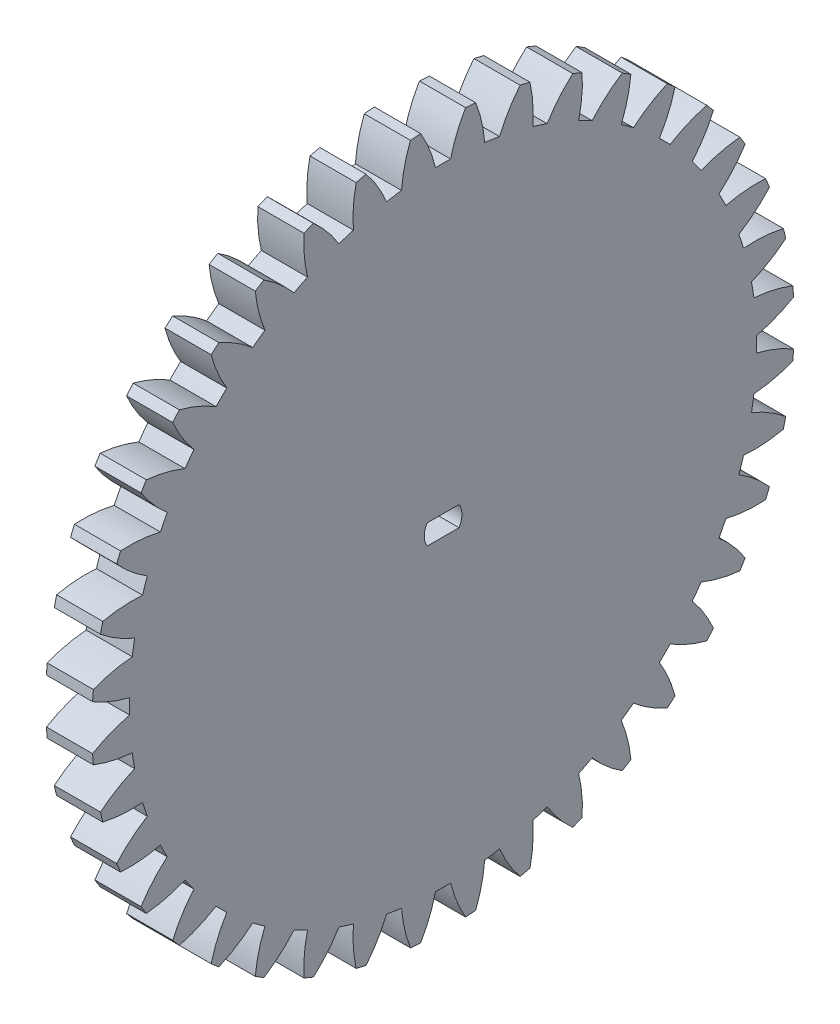
SolidWorks part; units mm, degrees
ref_plane "Plane1" through (0, 0, 0) normal (0, 0, 1) x (1, 0, 0)
ref_plane "Plane2" through (0, 0, 0) normal (0, 1, 0) x (1, 0, 0)
ref_plane "Plane3" through (0, 0, 0) normal (1, 0, 0) x (0, 0, -1)
sketch "HoldingSke" plane through (0, 0, 0) normal (0, 1, 0) x (1, 0, 0)
  line L0 (0, 0) -> (233.4903, -195.9217)
  line L1 (-15, 0) -> (100, 0) construction
  line L2 (0, 0) -> (-2.1039, 2.3779)
  line L3 (0, 0) -> (-11.863, 4.5341)
  line L4 (0, 0) -> (6.6156, 5.5511)
  line L5 (0, 0) -> (-47.5972, -17.7524)
  line L6 (0, 0) -> (-4.8428, -3.2675)
  line L7 (-2.1039, 2.3779) -> (8.8308, 51.9871)
  line L8 (-76.2, 54.61) -> (-71.1708, 54.61)
  line L9 (-71.009, 38.7566) -> (-53.1078, 45.2721)
  line L10 (-76.2, 71.12) -> (104.1128, 71.12)
  line L11 (0, 0) -> (-5.842, 0)
  line L12 (-76.2, 101.6) -> (-76.1147, 101.6)
  line L13 (24.9733, 27.94) -> (52.9518, 28.4284)
  line L14 (24.9733, 27.94) -> (24.9746, 27.94)
  line L15 (24.9733, 27.94) -> (100.4006, 29.5858)
  circle A0 centre (0, 0) radius 2.3813
  circle A1 centre (0, 0) radius 38.1
  circle A2 centre (0, 0) radius 38.1
  circle A3 centre (0, 0) radius 2.3813
  dimension "Num_teeth" = 40
  dimension "H" = 19.05
  dimension "Pitch_radius" = 180.3128
  dimension "Width" = 5.842
  dimension "Thickness" = 5.842
sketch "BasProSke" plane through (0, 0, 0) normal (0, 1, 0) x (1, 0, 0)
  line L0 (-10, 0) -> (60, 0) construction
  line L1 (0, 0) -> (0, 44.45)
  line L2 (0, 0) -> (5.842, 0)
  line L3 (5.842, 0) -> (5.842, 44.45)
  line L4 (5.842, 44.45) -> (0, 44.45)
  dimension "Thickness" = 5.842
  dimension "Diameter" = 88.9
revolve "Base-Revolve" add sketch "BasProSke" angle 360 about L0
sketch "TooCutSke" plane through (0, 0, 0) normal (1, 0, 0) x (0, 0, -1)
  line L1 (0, 0) -> (0, 107) construction
  line L2 (0, 0) -> (-1.8113, 42.2946) construction
  line L3 (0, 0) -> (-6.6386, 84.3518) construction
  line L4 (-1.8113, 42.2946) -> (-3.3193, 42.1759) construction
  arc A0 (0.958, 39.6747) -> (-0.958, 39.6747) centre (0, 0) ccw
  arc A1 (2.8603, 44.3833) -> (-2.8603, 44.3833) centre (0, 0) ccw
  circle A2 centre (0, 0) radius 42.3333 construction
  circle A3 centre (0, 0) radius 39.7803 construction
  arc A4 (-0.958, 39.6747) -> (-2.8603, 44.3833) centre (-17.432, 35.7575) ccw
  arc A5 (2.8603, 44.3833) -> (0.958, 39.6747) centre (17.432, 35.7575) ccw
extrude "ToothCut" cut sketch "TooCutSke" along normal through all
fillet "Breaks" [suppressed] radius 0.0423 tangent propagation no
fillet "RootFillets" [suppressed] radius 0.5304
pattern_circular "TeethCuts" count 40 every 9 about axis through (-10, 0, 0) along (1, 0, 0) of "ToothCut", "RootFillets", "Breaks"
sketch "HubNeaOneSke" plane through (0, 0, 0) normal (-1, 0, 0) x (0, 0, 1)
  circle A0 centre (0, 0) radius 38.1
  dimension "Diameter" = 76.2
extrude "HubNearOne" [suppressed] add sketch "HubNeaOneSke" along normal blind 44.9581
sketch "HubNeaBotSke" plane through (0, 0, 0) normal (-1, 0, 0) x (0, 0, 1)
  circle A0 centre (0, 0) radius 38.1
  dimension "Diameter" = 76.2
extrude "HubNearBoth" [suppressed] add sketch "HubNeaBotSke" along normal blind 22.479
ref_plane "FarPln" through (5.842, 0, 0) normal (1, 0, 0) x (0, 0, -1)
sketch "HubFarSke" plane through (5.842, 0, 0) normal (1, 0, 0) x (0, 0, -1)
  circle A0 centre (0, 0) radius 38.1
  dimension "Diameter" = 76.2
extrude "HubFar" [suppressed] add sketch "HubFarSke" along normal blind 22.479
sketch "BorSke" plane through (0, 0, 0) normal (1, 0, 0) x (0, 0, -1)
  circle A0 centre (0, 0) radius 2.3813
  dimension "Diameter" = 4.7625
extrude "Bore" cut sketch "BorSke" along normal mid plane 101.6001
sketch "KeySke" plane through (0, 0, 0) normal (1, 0, 0) x (0, 0, -1)
  line L0 (-0.127, 0) -> (-0.127, 2.648)
  line L1 (-0.127, 2.648) -> (0.127, 2.648)
  line L2 (0.127, 2.648) -> (0.127, 0)
  line L3 (0, 0) -> (0, 34) construction
  line L4 (-0.127, 0) -> (0.127, 0)
  dimension "Width" = 0.254
extrude "Keyway" [suppressed] cut sketch "KeySke" along normal mid plane 101.6001
pattern_circular "Keyway2" [suppressed] count 2 every 90 about axis through (-10, 0, 0) along (1, 0, 0) reverse direction yes
sketch "Sketch1" plane through (5.842, 0, 0) normal (1, 0, 0) x (0, 0, -1)
  line L0 (-2.0143, 1.27) -> (2.0143, 1.27)
  line L1 (-2.0143, -1.27) -> (2.0143, -1.27)
  line L2 (0, 1.27) -> (0, -1.27) construction
  circle A0 centre (0, 0) radius 2.3813 construction
  arc A1 (-2.0143, -1.27) -> (2.0143, -1.27) centre (0, 0) ccw
  arc A2 (2.0143, 1.27) -> (-2.0143, 1.27) centre (0, 0) ccw
  point P11 (0, 0)
  dimension "D1" = 2.54
extrude "Boss-Extrude1" add sketch "Sketch1" against normal up to surface (5.842 mm away) up to face at (0, 0, -2.3813)
equation "' \"Pitch@HoldingSke\" = 4"
equation "' \"Num_teeth@HoldingSke\" = 12"
equation "' \"Ap@HoldingSke\" =  20"
equation "' \"Ap@HoldingSke\" = 20"
equation "' \"Width@HoldingSke\" = 0.5"
equation "' \"Hub_dia@HoldingSke\"= 1"
equation "' \"Hub_dia@HoldingSke\" = 1"
equation "' \"Overall_len@HoldingSke\" = 1.0"
equation "' \"Bore@HoldingSke\" = 0.75"
equation "' \"T_dim@HoldingSke\" = 0.85"
equation "' \"Width@KeySke\" = 0.25"
equation "' \"Show_teeth@HoldingSke\" = 13"
equation "' \"Backlash@HoldingSke\" = 0.009"
equation "' \"Addendum_fac@HoldingSke\" = 1.0"
equation "' \"Dedendum_fac@HoldingSke\" = 1.25"
equation "' \"Dedendum_add@HoldingSke\" = 0.00005"
equation "' \"Clearance_fac@HoldingSke\" = 0.25"
equation "' \"Pitch@HoldingSke\" = 0.5"
equation "' \"Num_teeth@HoldingSke\" = 23"
equation "' \"Show_teeth@HoldingSke\" = 23"
equation "' \"Backlash@HoldingSke\" = 0.0375"
equation "\"Overcut_dia@TooCutSke\" = (\"Num_teeth@HoldingSke\" + 2 * \"Addendum_fac@HoldingSke\") / \"Pitch@HoldingSke\" + 0.002"
equation "\"Pitch_dia@TooCutSke\" = \"Num_teeth@HoldingSke\" / \"Pitch@HoldingSke\""
equation "\"Base_dia@TooCutSke\" = \"Num_teeth@HoldingSke\" / \"Pitch@HoldingSke\" * cos((\"Ap@HoldingSke\"  * 3.14159265 / 180))"
equation "\"Root_dia@TooCutSke\" = (\"Num_teeth@HoldingSke\" + 2) / \"Pitch@HoldingSke\" - 2 * (\"Addendum_fac@HoldingSke\" + \"Dedendum_fac@HoldingSke\") / \"Pitch@HoldingSke\" - \"Dedendum_add@HoldingSke\" * 2"
equation "\"Half_ang@TooCutSke\" = 180 / \"Num_teeth@HoldingSke\""
equation "\"Half_CT@TooCutSke\" = \"Num_teeth@HoldingSke\" / \"Pitch@HoldingSke\" * sin((3.14159265 / 2 / \"Num_teeth@HoldingSke\")) / 2 - 7 * \"Backlash@HoldingSke\" / 4"
equation "\"Flank_rad@TooCutSke\" = \"Num_teeth@HoldingSke\" / \"Pitch@HoldingSke\" / 5"
equation "\"Radius@RootFillets\" = \"Clearance_fac@HoldingSke\" / \"Pitch@HoldingSke\" + \"Dedendum_add@HoldingSke\""
equation "\"Break_rad@Breaks\" = 0.02 / \"Pitch@HoldingSke\""
equation "\"Thickness@HoldingSke\" = \"Width@HoldingSke\""
equation "\"OAL@HoldingSke\" = \"Thickness@HoldingSke\""
equation "\"MHD@HoldingSke\" = (\"Num_teeth@HoldingSke\" + 2) / \"Pitch@HoldingSke\" - 2 * (\"Addendum_fac@HoldingSke\" + \"Dedendum_fac@HoldingSke\")  / \"Pitch@HoldingSke\" - \"Dedendum_add@HoldingSke\" * 2"
equation "\"MBD@HoldingSke\" = (\"Num_teeth@HoldingSke\" + 2) / \"Pitch@HoldingSke\" - 2 * (\"Addendum_fac@HoldingSke\" + \"Dedendum_fac@HoldingSke\")  / \"Pitch@HoldingSke\" - \"Dedendum_add@HoldingSke\" * 2 - 0.002"
equation "\"MHD@HoldingSke\" = ((sgn( \"MHD@HoldingSke\" - \"Hub_dia@HoldingSke\" )-1)*( \"MHD@HoldingSke\" - \"Hub_dia@HoldingSke\" ))/-2+ \"Hub_dia@HoldingSke\""
equation "\"MBD@HoldingSke\" = ((sgn( \"MBD@HoldingSke\" - \"Bore@HoldingSke\" )-1)*( \"MBD@HoldingSke\" - \"Bore@HoldingSke\" ))/-2+ \"Bore@HoldingSke\""
equation "\"OAL@HoldingSke\" = ((sgn( \"OAL@HoldingSke\" - \"Overall_len@HoldingSke\" )+1)*( \"OAL@HoldingSke\" - \"Overall_len@HoldingSke\" ))/2 + \"Overall_len@HoldingSke\" + 0.000002"
equation "\"Num_teeth@TeethCuts\" = int( \"Show_teeth@HoldingSke\" ) + 1"
equation "\"Num_teeth@TeethCuts\" = ((sgn( \"Num_teeth@TeethCuts\" - \"Num_teeth@HoldingSke\" )-1)*( \"Num_teeth@TeethCuts\" - \"Num_teeth@HoldingSke\" ))/-2+ \"Num_teeth@HoldingSke\""
equation "\"Num_teeth@TeethCuts\" = ((sgn( \"Num_teeth@TeethCuts\" - 2.0)+1)*( \"Num_teeth@TeethCuts\" - 2.0))/2 +2.0"
equation "\"Angle@TeethCuts\" = 360.0 / \"Num_teeth@HoldingSke\""
equation "\"Diameter@BasProSke\" = (\"Num_teeth@HoldingSke\" + 2 * \"Addendum_fac@HoldingSke\") / \"Pitch@HoldingSke\""
equation "\"Thickness@BasProSke\"  = \"Thickness@HoldingSke\""
equation "' \"Fillet_rad@BasProSke\" =  \"Thickness@HoldingSke\" * 0.05"
equation "' \"Fillet_rad@BasProSke\" = \"Thickness@HoldingSke\" * 0.05"
equation "\"MHD@HoldingSke\" = ((sgn( \"MHD@HoldingSke\" - \"Root_dia@TooCutSke\" )-1)*( \"MHD@HoldingSke\" - \"Root_dia@TooCutSke\" ))/-2+ \"Root_dia@TooCutSke\""
equation "\"Diameter@HubNeaOneSke\" = \"MHD@HoldingSke\""
equation "\"Length@HubNearOne\" = \"OAL@HoldingSke\" - \"Thickness@BasProSke\""
equation "\"Diameter@HubNeaBotSke\" = \"MHD@HoldingSke\""
equation "\"Length@HubNearBoth\" = ( \"OAL@HoldingSke\" - \"Thickness@BasProSke\" ) / 2.0"
equation "\"Thickness@FarPln\" = \"Thickness@BasProSke\""
equation "\"Diameter@HubFarSke\" = \"MHD@HoldingSke\""
equation "\"Length@HubFar\" = ( \"OAL@HoldingSke\" - \"Thickness@BasProSke\" ) / 2.0"
equation "\"Diameter@BorSke\" = \"MBD@HoldingSke\""
equation "\"D1@Bore\" = \"OAL@HoldingSke\" * 2.0"
equation "\"D1@Keyway\" = \"OAL@HoldingSke\" * 2.0"
equation "\"Offset@KeySke\" = \"T_dim@HoldingSke\" - \"MBD@HoldingSke\" / 2.0"
